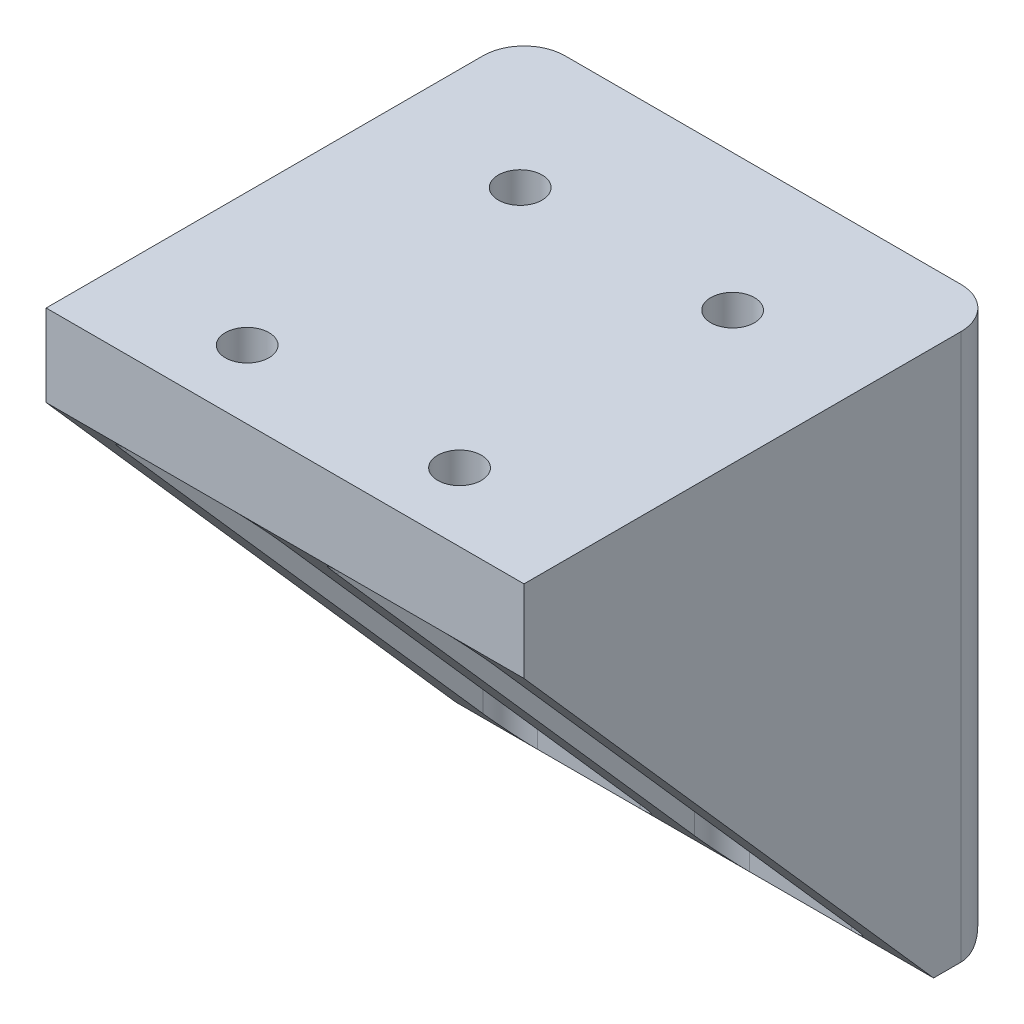
SolidWorks part; units mm, degrees
ref_plane "Front Plane" through (0, 0, 0) normal (0, 0, 1) x (1, 0, 0)
ref_plane "Top Plane" through (0, 0, 0) normal (0, 1, 0) x (1, 0, 0)
ref_plane "Right Plane" through (0, 0, 0) normal (1, 0, 0) x (0, 0, -1)
sketch "HT2205 BLDC" plane through (0, 0, 0) normal (0, 0, 1) x (1, 0, 0)
  line L0 (-7.7782, 7.7782) -> (0, 0) construction
  line L1 (0, 0) -> (0, 11) construction
  circle A0 centre (0, 0) radius 11 construction
  circle A1 centre (-7.7782, 7.7782) radius 1 construction
  circle A2 centre (7.7782, 7.7782) radius 1 construction
  circle A3 centre (7.7782, -7.7782) radius 1 construction
  circle A4 centre (-7.7782, -7.7782) radius 1 construction
  circle A5 centre (0, 0) radius 13.15 construction
  point P15 (0, 0)
  dimension "D1" = 22
  dimension "D2" = 2
  dimension "D6" = 26.3
  dimension "D3" = 45
  dimension "D5" = 15.5563
  dimension "D4" = 4
sketch "Sketch3" plane through (0, 0, 0) normal (0, 0, 1) x (1, 0, 0)
  line L1 (-17.5, -20) -> (17.5, -20)
  line L2 (-17.5, -20) -> (-17.5, 20)
  line L3 (-17.5, 20) -> (17.5, 20)
  line L4 (17.5, -20) -> (17.5, 20)
  line L5 (-17.5, -20) -> (17.5, 20) construction
  line L6 (-17.5, 20) -> (17.5, -20) construction
  point P0 (0, 0)
  point P6 (17.7654, 20)
  dimension "D1" = 20
  dimension "D2" = 35
extrude "Boss-Extrude1" add sketch "Sketch3" along normal blind 5
sketch "Sketch5" plane through (0, 20, 0) normal (0, 1, 0) x (1, 0, 0)
  line L0 (-17.5, -5) -> (17.5, -5)
  line L1 (-17.5, -5) -> (-17.5, -35)
  line L2 (17.5, -5) -> (17.5, -35)
  line L3 (-17.5, -35) -> (17.5, -35)
  dimension "D1" = 30
extrude "Boss-Extrude2" add sketch "Sketch5" against normal blind 6
sketch "Sketch7" plane through (17.5, 0, 0) normal (1, 0, 0) x (0, 0, -1)
  line L0 (-35, 14) -> (-5, -20)
  line L1 (-5, -20) -> (-5, 14)
  line L2 (-5, 14) -> (-35, 14)
extrude "Boss-Extrude3" add sketch "Sketch7" against normal blind 4
mirror "Mirror1" about plane through (0, 0, 0) normal (1, 0, 0) of "Boss-Extrude3"
sketch "Sketch8" plane through (0, 0, 0) normal (1, 0, 0) x (0, 0, -1)
  line L0 (-35, 14) -> (-5, -20)
  line L1 (-5, -20) -> (-5, 14)
  line L2 (-5, 14) -> (-35, 14)
extrude "Boss-Extrude4" add sketch "Sketch8" along normal blind 2 and the other way blind 2
sketch "Sketch9" plane through (0, 0, 0) normal (0, 0, -1) x (-1, 0, 0)
  circle A0 centre (-7.7782, 7.7782) radius 1.05
  circle A1 centre (7.7782, 7.7782) radius 1.05
  circle A2 centre (7.7782, -7.7782) radius 1.05
  circle A3 centre (-7.7782, -7.7782) radius 1.05
  dimension "D1" = 2.1
extrude "Cut-Extrude1" cut sketch "Sketch9" against normal blind 5
sketch "Sketch10" plane through (0, 20, 0) normal (0, 1, 0) x (1, 0, 0)
  line L0 (-7.7782, 0) -> (-7.7782, -35) construction
  line L1 (-8.7782, 0) -> (-6.7782, 0) construction
  line L2 (-17.5, -35) -> (17.5, -35) construction
  line L3 (7.7782, 0) -> (7.7782, -35) construction
  line L4 (6.7782, 0) -> (8.7782, 0) construction
  line L5 (-7.7782, -10) -> (7.7782, -10) construction
  line L6 (-7.7782, -30) -> (7.7782, -30) construction
  line L7 (-11, 0) -> (11, 0) construction
  circle A0 centre (-7.7782, -10) radius 1.6
  circle A1 centre (-7.7782, -30) radius 1.6
  circle A2 centre (7.7782, -30) radius 1.6
  circle A3 centre (7.7782, -10) radius 1.6
  dimension "D1" = 3.2
  dimension "D2" = 10
  dimension "D3" = 20
extrude "Cut-Extrude2" cut sketch "Sketch10" against normal through all
fillet "Fillet1" radius 3 3 edges at (-17.5, 0, 0) (0, -20, 0) (17.5, 0, 0)
fillet "Fillet2" radius 2 8 edges at (-13.5, 14, 20) (-2, 14, 20) (2, 14, 20) (13.5, 14, 20) (13.5, -3, 5) (2, -3, 5) (-13.5, -3, 5) (-2, -3, 5)
